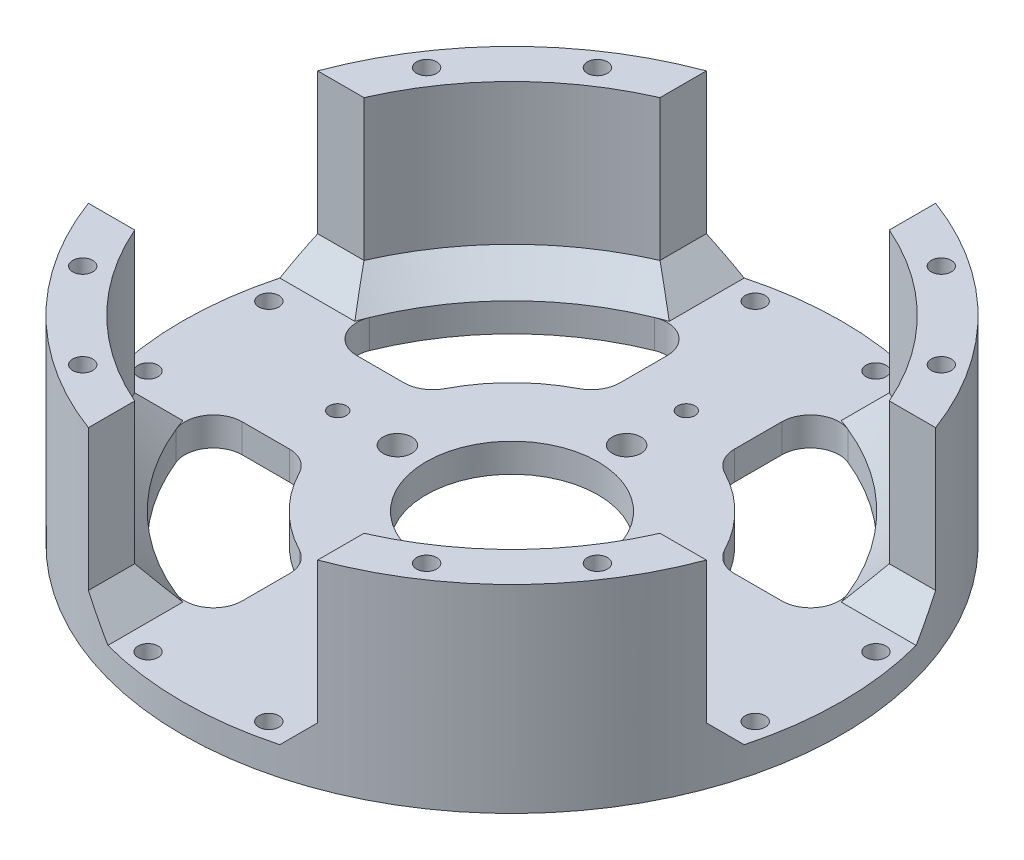
SolidWorks part; units mm, degrees
ref_plane "Front Plane" through (0, 0, 0) normal (0, 0, 1) x (1, 0, 0)
ref_plane "Top Plane" through (0, 0, 0) normal (0, 1, 0) x (1, 0, 0)
ref_plane "Right Plane" through (0, 0, 0) normal (1, 0, 0) x (0, 0, -1)
sketch "Sketch1" plane through (0, 0, 0) normal (0, 1, 0) x (1, 0, 0)
  circle A0 centre (0, 0) radius 57.5
  dimension "D1" = 115
extrude "Boss-Extrude1" add sketch "Sketch1" along normal blind 34.6
sketch "Sketch2" plane through (0, 34.6, 0) normal (0, 1, 0) x (1, 0, 0)
  circle A0 centre (0, 0) radius 50
  dimension "D1" = 100
extrude "Cut-Extrude1" cut sketch "Sketch2" against normal blind 29.6
sketch "Sketch3" plane through (0, 0, 0) normal (0, -1, 0) x (1, 0, 0)
  line L0 (0, 62.4892) -> (0, -59.6631) construction
  line L1 (-72.2237, 0) -> (67.9845, 0) construction
  line L6 (43.8748, 10) -> (43.8748, -10)
  line L7 (43.8748, 10) -> (25.6174, 10)
  line L8 (43.8748, -10) -> (25.6174, -10)
  line L9 (25.6174, 10) -> (25.6174, -10)
  line L10 (-10, -43.8748) -> (10, -43.8748)
  line L11 (-10, -43.8748) -> (-10, -25.6174)
  line L12 (10, -43.8748) -> (10, -25.6174)
  line L13 (-10, -25.6174) -> (10, -25.6174)
  line L14 (-43.8748, 10) -> (-43.8748, -10)
  line L15 (-43.8748, 10) -> (-25.6174, 10)
  line L16 (-43.8748, -10) -> (-25.6174, -10)
  line L17 (-25.6174, 10) -> (-25.6174, -10)
  line L18 (-10, 43.8748) -> (10, 43.8748)
  line L19 (-10, 43.8748) -> (-10, 25.6174)
  line L20 (10, 43.8748) -> (10, 25.6174)
  line L21 (-10, 25.6174) -> (10, 25.6174)
  circle A0 centre (0, 0) radius 20 construction
  circle A1 centre (0, 0) radius 15
  circle A2 centre (0, 20) radius 2.5
  circle A3 centre (20, 0) radius 2.5
  circle A4 centre (0, -20) radius 2.5
  circle A5 centre (-20, 0) radius 2.5
  circle A6 centre (0, 0) radius 27.5
  circle A7 centre (0, 0) radius 45
  point P15 (0, 0)
  dimension "D1" = 40
  dimension "D2" = 30
  dimension "D3" = 5
  dimension "D5" = 55
  dimension "D6" = 90
  dimension "D7" = 20
  dimension "D4" = 4
extrude "Cut-Extrude2" cut sketch "Sketch3" against normal blind 31.8 contours L19 A7 L15 A6 | L7 A7 L20 A6 | L12 A7 L8 A6 | L16 A7 L11 A6 | A5 | A1 | A2 | A3 | A4
sketch "Sketch4" plane through (0, 0, 0) normal (0, -1, 0) x (1, 0, 0)
  line L0 (0, 0) -> (-10.5349, 52.9624) construction
  line L1 (30.4056, 0) -> (0, 30.4056) construction
  line L2 (0, 30.4056) -> (-30.4056, 0) construction
  line L3 (-30.4056, 0) -> (0, -30.4056) construction
  line L4 (0, -30.4056) -> (30.4056, 0) construction
  line L5 (0, 0) -> (69.7116, 0) construction
  line L6 (0, 0) -> (0, 54) construction
  circle A0 centre (0, 0) radius 54 construction
  circle A13 centre (0, 0) radius 21.5 construction
  circle A14 centre (0, 30.4056) radius 1.5
  circle A15 centre (30.4056, 0) radius 1.5
  circle A16 centre (0, -30.4056) radius 1.5
  circle A17 centre (-30.4056, 0) radius 1.5
  circle A22 centre (-10.5349, 52.9624) radius 1.75
  circle A23 centre (10.5349, 52.9624) radius 1.75
  circle A24 centre (30.0008, 44.8994) radius 1.75
  circle A25 centre (44.8994, 30.0008) radius 1.75
  circle A26 centre (52.9624, 10.5349) radius 1.75
  circle A27 centre (52.9624, -10.5349) radius 1.75
  circle A28 centre (44.8994, -30.0008) radius 1.75
  circle A29 centre (30.0008, -44.8994) radius 1.75
  circle A30 centre (10.5349, -52.9624) radius 1.75
  circle A31 centre (-10.5349, -52.9624) radius 1.75
  circle A32 centre (-30.0008, -44.8994) radius 1.75
  circle A33 centre (-44.8994, -30.0008) radius 1.75
  circle A34 centre (-52.9624, -10.5349) radius 1.75
  circle A35 centre (-52.9624, 10.5349) radius 1.75
  circle A36 centre (-44.8994, 30.0008) radius 1.75
  circle A37 centre (-30.0008, 44.8994) radius 1.75
  point P29 (0, 0)
  point P43 (0, 0)
  point P54 (0, 0)
  dimension "D1" = 108
  dimension "D2" = 11.25
  dimension "D5" = 3
  dimension "D3" = 3.5
  dimension "D4" = 43
  dimension "D7" = 16
  dimension "D6" = 4
extrude "Cut-Extrude3" cut sketch "Sketch4" against normal blind 50
sketch "Sketch6" plane through (0, 0, 0) normal (0, 0, 1) x (1, 0, 0)
  line L0 (0, -2.1266) -> (0, 59.0209)
sketch "Sketch9" plane through (0, 0, 0) normal (0, 0, 1) x (1, 0, 0)
  line L0 (0, -2.1266) -> (0, 59.0209) construction
  line L1 (-20, 34.6) -> (20, 34.6)
  line L2 (-20, 34.6) -> (-20, 5)
  line L3 (-20, 5) -> (20, 5)
  line L4 (20, 34.6) -> (20, 5)
  line L5 (-20, 34.6) -> (20, 5) construction
  line L6 (-20, 5) -> (20, 34.6) construction
  line L7 (50, 34.6) -> (-50, 34.6) construction
  line L8 (-57.5, 0) -> (57.5, 0) construction
  point P0 (0, 19.8)
  dimension "D1" = 5
  dimension "D2" = 40
extrude "Cut-Extrude4" cut sketch "Sketch9" against normal blind 72
pattern_circular "CirPattern1" count 4 over 360 about axis through (0, 0, 0) along (0, 1, 0) of "Cut-Extrude4"
fillet "Fillet2" radius 5 16 edges at (-25.6174, 2.5, 10) (-10, 2.5, 25.6174) (-10, 2.5, 43.8748) (-43.8748, 2.5, 10) (43.8748, 2.5, 10) (25.6174, 2.5, 10) (10, 2.5, 25.6174) (10, 2.5, 43.8748) (10, 2.5, -25.6174) (25.6174, 2.5, -10) (43.8748, 2.5, -10) (10, 2.5, -43.8748) (-25.6174, 2.5, -10) (-10, 2.5, -25.6174) (-10, 2.5, -43.8748) (-43.8748, 2.5, -10)
chamfer "Chamfer1" distance 5 angle 45 12 edges at (-35.3553, 5, -35.3553) (-20, 5, -49.8677) (20, 5, -49.8677) (-35.3553, 5, 35.3553) (35.3553, 5, 35.3553) (35.3553, 5, -35.3553) (-49.8677, 5, 20) (20, 5, 49.8677) (49.8677, 5, -20) (49.8677, 5, 20) (-20, 5, 49.8677) (-49.8677, 5, -20)
